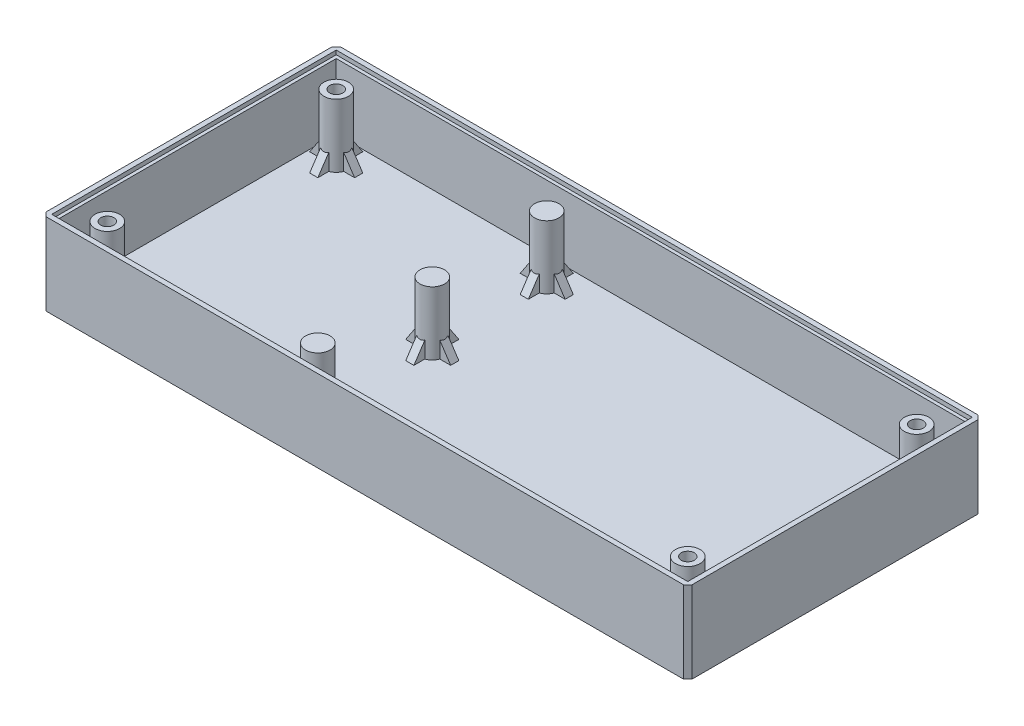
SolidWorks part; units mm, degrees
ref_plane "Front Plane" through (0, 0, 0) normal (0, 0, 1) x (1, 0, 0)
ref_plane "Top Plane" through (0, 0, 0) normal (0, 1, 0) x (1, 0, 0)
ref_plane "Right Plane" through (0, 0, 0) normal (1, 0, 0) x (0, 0, -1)
sketch "Sketch1" plane through (0, 0, 0) normal (0, 1, 0) x (1, 0, 0)
  line L0 (-77, 34) -> (-77, -34)
  line L1 (-76, 33) -> (76, 33) construction
  line L2 (-76, 33) -> (-76, -33) construction
  line L3 (-76, -33) -> (76, -33) construction
  line L4 (76, 33) -> (76, -33) construction
  line L5 (-76, 33) -> (76, -33) construction
  line L6 (-76, -33) -> (76, 33) construction
  line L7 (-77, -34) -> (77, -34)
  line L8 (77, 34) -> (77, -34)
  line L9 (-77, 34) -> (77, 34)
  line L10 (-79, -36) -> (79, -36)
  line L15 (-68, -18.1) -> (-51, -18.1) construction
  line L16 (-68, -18.1) -> (-68, 15.9) construction
  line L17 (-68, 15.9) -> (-51, 15.9) construction
  line L18 (-51, -18.1) -> (-51, 15.9) construction
  line L19 (-68, -18.1) -> (-51, 15.9) construction
  line L20 (-68, 15.9) -> (-51, -18.1) construction
  line L21 (-68.2, -18.6) -> (-50.8, -18.6)
  line L22 (-68.2, -18.6) -> (-68.2, 16.4)
  line L23 (-68.2, 16.4) -> (-50.8, 16.4)
  line L24 (-50.8, -18.6) -> (-50.8, 16.4)
  line L25 (-68.2, -18.6) -> (-50.8, 16.4) construction
  line L26 (-68.2, 16.4) -> (-50.8, -18.6) construction
  line L27 (79, 36) -> (79, -36)
  line L28 (-79, 36) -> (79, 36)
  line L29 (-79, 36) -> (-79, -36)
  circle A0 centre (-71, 28) radius 1.6
  circle A1 centre (-71, 28) radius 3
  circle A2 centre (71, 28) radius 3
  circle A3 centre (71, 28) radius 1.6
  circle A4 centre (71, -28) radius 3
  circle A5 centre (71, -28) radius 1.6
  circle A6 centre (-71, -28) radius 3
  circle A7 centre (-71, -28) radius 1.6
  circle A8 centre (-19.5, 28) radius 3
  circle A9 centre (-19.5, 28) radius 1.6
  circle A10 centre (-19.5, -28) radius 3
  circle A11 centre (-19.5, -28) radius 1.6
  circle A12 centre (-19.5, 0) radius 3
  circle A13 centre (-19.5, 0) radius 1.6
  point P0 (0, 0)
  point P14 (-59.5, -1.1)
  point P27 (-59.5, -1.1)
  dimension "D4" = 3.2
  dimension "D5" = 5
  dimension "D6" = 5
  dimension "D7" = 6
  dimension "D19" = 142
  dimension "D20" = 51.5
  dimension "D1" = 152
  dimension "D2" = 66
  dimension "D10" = 17
  dimension "D11" = 34
  dimension "D12" = 8
  dimension "D13" = 17.1
  dimension "D14" = 35
  dimension "D15" = 17.4
  dimension "D3" = 1
  dimension "D16" = 2
  dimension "D8" = 2
  dimension "D9" = 2
  dimension "D17" = 2
  dimension "D18" = 2
extrude "Boss-Extrude1" add sketch "Sketch1" along normal blind 3 contours A3 | A0 | A7 | A5 | L0 L7 L8 L9 region at (-71, 0, -28) region at (71, 0, -28) region at (71, 0, 28) region at (-71, 0, 28)
extrude "Boss-Extrude2" add sketch "Sketch1<4>" along normal blind 19 contours L28 L29 L10 L27 L0 L9 L8 L7 region at (-77.2637, 0, 0)
sketch "Sketch1<4>" plane through (0, 0, 0) normal (0, 1, 0) x (1, 0, 0) same geometry as "Sketch1"
sketch "Sketch2" plane through (0, 19, 0) normal (0, 1, 0) x (1, 0, 0)
  line L0 (-77.8, 34.8) -> (-77.8, -34.8)
  line L1 (-79, 36) -> (79, 36)
  line L2 (-79, 36) -> (-79, -36)
  line L3 (-79, -36) -> (79, -36)
  line L4 (79, 36) -> (79, -36)
  line L5 (-77.8, -34.8) -> (77.8, -34.8)
  line L6 (77.8, 34.8) -> (77.8, -34.8)
  line L7 (-77.8, 34.8) -> (77.8, 34.8)
  dimension "D1" = 1.2
extrude "Boss-Extrude3" add sketch "Sketch2" along normal blind 1
extrude "Boss-Extrude4" add sketch "Sketch1<5>" along normal blind 18.5 contours A1 A0 | A2 A3 | A4 A5 | A6 A7 | A8 | A12 | A10 region at (-73.9151, 0, -28) region at (68.0849, 0, -28) region at (68.0849, 0, 28) region at (-73.9151, 0, 28)
sketch "Sketch1<5>" plane through (0, 0, 0) normal (0, 1, 0) x (1, 0, 0) same geometry as "Sketch1"
sketch "Sketch3" plane through (0, 0, 0) normal (0, -1, 0) x (1, 0, 0)
  line L0 (-68.8349, 24.25) -> (-66.6699, 28)
  line L1 (-69.4123, 25.25) -> (-67.8246, 28)
  line L2 (-67.8246, 28) -> (-69.4123, 30.75)
  line L3 (-69.4123, 30.75) -> (-72.5877, 30.75)
  line L4 (-72.5877, 30.75) -> (-74.1754, 28)
  line L5 (-74.1754, 28) -> (-72.5877, 25.25)
  line L6 (-72.5877, 25.25) -> (-69.4123, 25.25)
  line L7 (-66.6699, 28) -> (-68.8349, 31.75)
  line L8 (-68.8349, 31.75) -> (-73.1651, 31.75)
  line L9 (-73.1651, 31.75) -> (-75.3301, 28)
  line L10 (-75.3301, 28) -> (-73.1651, 24.25)
  line L11 (-73.1651, 24.25) -> (-68.8349, 24.25)
  circle A0 centre (-71, 28) radius 2.75 construction
  circle M20 centre (-71, 28) radius 1.6
  dimension "D1" = 5.5
  dimension "D2" = 1
extrude "Boss-Extrude5" add sketch "Sketch3<3>" against normal blind 2
sketch "Sketch3<3>" plane through (0, 0, 0) normal (0, -1, 0) x (1, 0, 0) same geometry as "Sketch3"
extrude "Cut-Extrude1" cut sketch "Sketch3" against normal blind 2 contours L5 L6 L1 L2 L3 L4 M20 region at (-71, 0, 25.334)
pattern_linear "LPattern1" count 2 spacing 142 along (1, 0, 0) count 2 spacing 56 along (0, 0, -1) of "Cut-Extrude1", "Boss-Extrude5"
chamfer "Chamfer1" distance 1 angle 45 4 edges at (-79, 10, 36) (-79, 10, -36) (79, 10, 36) (79, 10, -36)
ref_plane "Plane1" through (0, 0, -28) normal (0, 0, 1) x (1, 0, 0)
sketch "Sketch6" plane through (0, 0, -28) normal (0, 0, 1) x (1, 0, 0)
  line L0 (65.5, 3) -> (69.5, 9)
  line L1 (-77, 3) -> (77, 3) construction
  line L2 (68, 18.5) -> (68, 3) construction
  dimension "D1" = 2.5
  dimension "D2" = 6
  dimension "D3" = 4
rib "Rib1" sketch "Sketch6" sketch "Sketch6" thickness 2 extrusion direction parallel to sketch draft on no parameters "D1"=2
pattern_circular "CirPattern3" count 4 every 90 about axis through (71, 3, -28) along (0, 1, 0) of "Rib1"
pattern_linear "LPattern2" count 2 spacing 142 along (-1, 0, 0) count 2 spacing 56 along (0, 0, 1) of "CirPattern3"
sketch "Sketch7" plane through (0, 0, -28) normal (0, 0, 1) x (1, 0, 0)
  line L0 (-25, 3) -> (-21, 9)
  line L1 (-77, 3) -> (77, 3) construction
  line L2 (-22.5, 18.5) -> (-22.5, 3) construction
  point P6 (0, 0)
  dimension "D1" = 2.5
  dimension "D2" = 4
  dimension "D3" = 6
rib "Rib2" sketch "Sketch7" sketch "Sketch7" thickness 2 extrusion direction parallel to sketch draft on no parameters "D1"=2
pattern_circular "CirPattern4" count 4 every 90 about axis through (-19.5, 18.5, -28) along (0, 1, 0) of "Rib2"
pattern_linear "LPattern8" count 3 spacing 28 along (0, 0, 1) of "CirPattern4"
